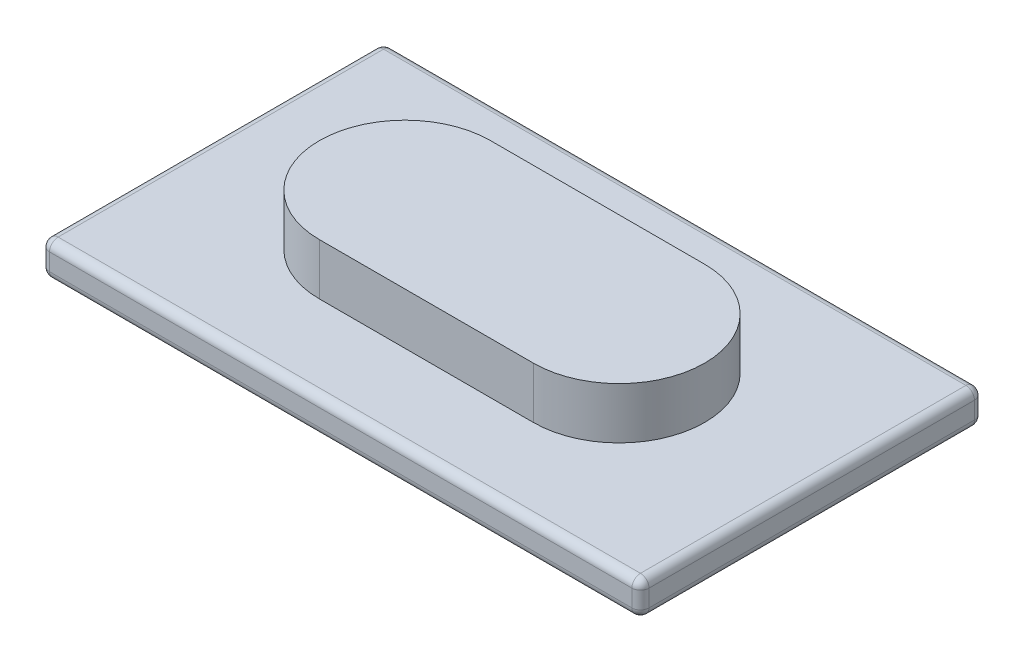
SolidWorks part; units mm, degrees
material "Mahogany"
ref_plane "Front Plane" through (0, 0, 0) normal (0, 0, 1) x (1, 0, 0)
ref_plane "Top Plane" through (0, 0, 0) normal (0, 1, 0) x (1, 0, 0)
ref_plane "Right Plane" through (0, 0, 0) normal (1, 0, 0) x (0, 0, -1)
sketch "Sketch1" plane through (0, 0, 0) normal (0, 1, 0) x (1, 0, 0)
  line L1 (-350, 200) -> (350, 200)
  line L2 (-350, 200) -> (-350, -200)
  line L3 (-350, -200) -> (350, -200)
  line L4 (350, 200) -> (350, -200)
  line L5 (-350, 200) -> (350, -200) construction
  line L6 (-350, -200) -> (350, 200) construction
  point P0 (0, 0)
  dimension "D1" = 700
  dimension "D2" = 400
extrude "Boss-Extrude1" add sketch "Sketch1" along normal blind 40
fillet "Fillet1" radius 10 12 edges at (350, 0, 0) (0, 0, -200) (-350, 0, 0) (0, 0, 200) (350, 40, 0) (0, 40, -200) (-350, 40, 0) (0, 40, 200) (350, 20, 200) (-350, 20, -200) (350, 20, -200) (-350, 20, 200)
sketch "Sketch2" plane through (0, 40, 0) normal (0, 1, 0) x (1, 0, 0)
  line L1 (-225, 100) -> (225, 100)
  line L2 (-225, 100) -> (-225, -100)
  line L3 (-225, -100) -> (225, -100)
  line L4 (225, 100) -> (225, -100)
  line L5 (-225, 100) -> (225, -100) construction
  line L6 (-225, -100) -> (225, 100) construction
  point P0 (0, 0)
  dimension "D1" = 450
  dimension "D2" = 200
extrude "Boss-Extrude2" add sketch "Sketch2" along normal blind 60
fillet "Fillet2" 2 edges at (225, 70, 100) (225, 70, -100) type full round first side face at (0, 70, 100) second side face at (0, 70, -100) middle face at (225, 70, 0)
fillet "Fillet3" 2 edges at (-225, 70, -100) (-225, 70, 100) type full round first side face at (-50, 70, -100) second side face at (-50, 70, 100) middle face at (-225, 70, 0)
sketch "Sketch3" plane through (0, 100, 0) normal (0, 1, 0) x (1, 0, 0)
  point P0 (0, 0)
